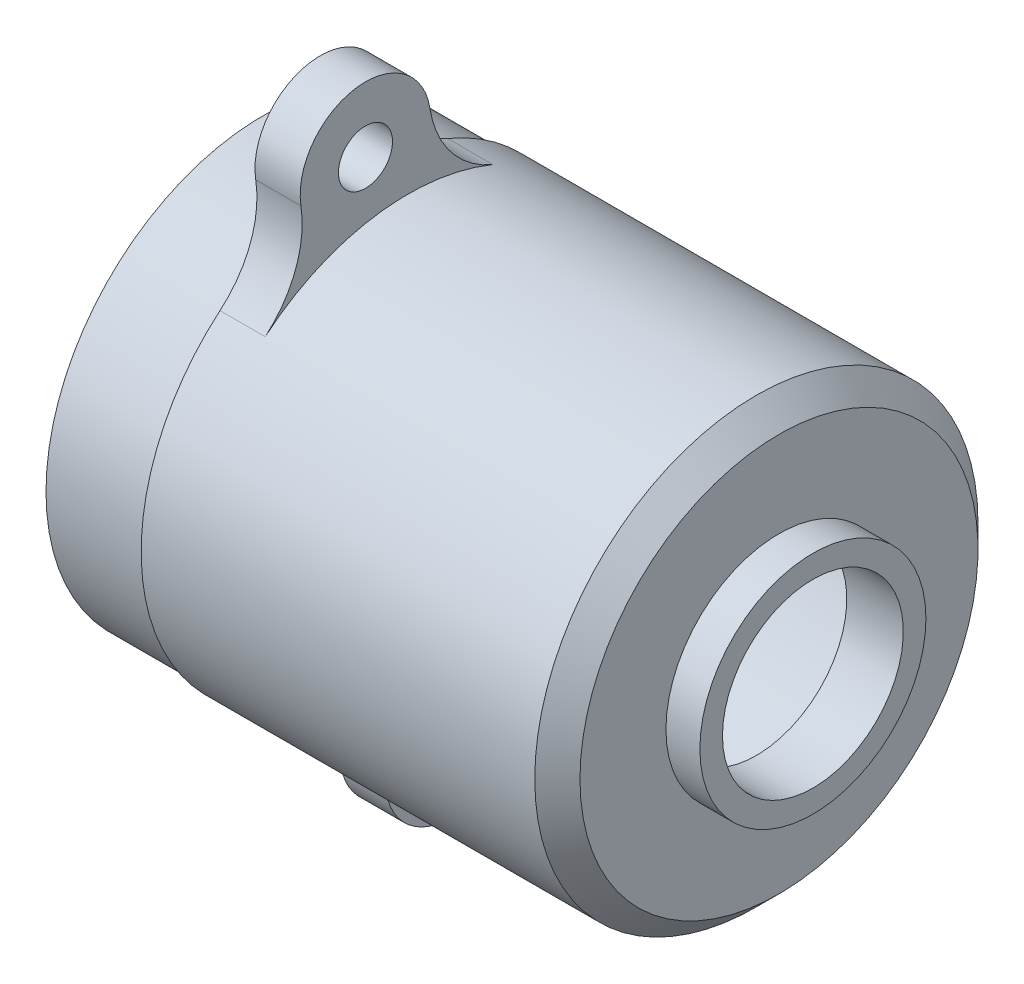
SolidWorks part; units mm, degrees
material "6061-T6 (SS)"
ref_plane "Front Plane" through (0, 0, 0) normal (0, 0, 1) x (1, 0, 0)
ref_plane "Top Plane" through (0, 0, 0) normal (0, 1, 0) x (1, 0, 0)
ref_plane "Right Plane" through (0, 0, 0) normal (1, 0, 0) x (0, 0, -1)
other "Center of Mass"
sketch "Sketch1" plane through (-31.75, 0, 0) normal (1, 0, 0) x (0, 0, -1)
  line L0 (0, 0) -> (-2.9885, 19.3009) construction
  line L1 (-0.1168, 15.7295) -> (1.5403, 20.0021) construction
  line L2 (1.5403, 20.0021) -> (-1.3314, 23.5735) construction
  line L3 (-1.3314, 23.5735) -> (-5.8601, 22.8723) construction
  line L4 (-5.8601, 22.8723) -> (-7.5172, 18.5996) construction
  line L5 (-7.5172, 18.5996) -> (-4.6456, 15.0282) construction
  line L6 (-4.6456, 15.0282) -> (-0.1168, 15.7295) construction
  line L7 (4.6456, -15.0282) -> (0.1168, -15.7295) construction
  line L8 (0.1168, -15.7295) -> (-1.5403, -20.0021) construction
  line L9 (-1.5403, -20.0021) -> (1.3314, -23.5735) construction
  line L10 (1.3314, -23.5735) -> (5.8601, -22.8723) construction
  line L11 (5.8601, -22.8723) -> (7.5172, -18.5996) construction
  line L12 (7.5172, -18.5996) -> (4.6456, -15.0282) construction
  line L13 (-7.5172, 18.5996) -> (1.5403, 20.0021) construction
  line L15 (0, 0) -> (12.0771, 1.87) construction
  circle A0 centre (0, 0) radius 13.9746
  circle A1 centre (0, 0) radius 15.5621 construction
  circle A3 centre (2.9885, -19.3009) radius 3.9688 construction
  circle A4 centre (-2.9885, 19.3009) radius 8.7404 construction
  arc A8 (-10.0273, 11.901) -> (-5.9586, -14.3762) centre (0, 0) ccw
  arc A9 (5.9586, 14.3762) -> (10.0273, -11.901) centre (0, 0) cw
  circle A16 centre (-2.9885, 19.3009) radius 2.667 construction
  circle A17 centre (2.9885, -19.3009) radius 2.667 construction
  arc A18 (-9.6776, 36.4316) -> (-11.5083, 22.6659) centre (127.0686, 11.2409) ccw construction
  arc A19 (4.4842, 36.4316) -> (4.6143, 28.807) centre (76.9988, 33.8561) ccw construction
  arc A20 (-10.0273, 11.901) -> (-7.5172, 18.5996) centre (-14.7303, 17.4828) ccw
  arc A21 (-7.5172, 18.5996) -> (1.5403, 20.0021) centre (-2.9885, 19.3009) cw
  arc A22 (1.5403, 20.0021) -> (5.9586, 14.3762) centre (8.7533, 21.1189) ccw
  arc A23 (7.5172, -18.5996) -> (10.0273, -11.901) centre (14.7303, -17.4828) cw
  arc A24 (-1.5403, -20.0021) -> (7.5172, -18.5996) centre (2.9885, -19.3009) ccw
  arc A25 (-5.9586, -14.3762) -> (-1.5403, -20.0021) centre (-8.7533, -21.1189) cw
  point P4 (-2.3812, 15.3788)
  dimension "D1" = 27.9492
  dimension "D4" = 5.334
  dimension "D2" = 1.5875
  dimension "D3" = 7.9375
extrude "Boss-Extrude1" add sketch "Sketch1" along normal blind 3.175
sketch "Sketch2" plane through (-28.575, 0, 0) normal (1, 0, 0) x (0, 0, -1)
  circle A0 centre (0, 0) radius 13.9746
  circle A1 centre (0, 0) radius 15.5621
  arc A2 (-10.0273, 11.901) -> (-5.9586, -14.3762) centre (0, 0) ccw construction
  circle A3 centre (0, 0) radius 13.9746 construction
extrude "Boss-Extrude2" add sketch "Sketch2" along normal up to surface (24.4625 mm away)
sketch "Sketch5" plane through (0, 0, 0) normal (0, 0, 1) x (1, 0, 0)
  line L1 (-0.1437, 7.9375) -> (-0.1437, 6.35)
  line L3 (-4.1125, -15.5621) -> (-4.1125, 15.5621) construction
  line L4 (-4.1125, 6.35) -> (-4.1125, 15.5621)
  line L5 (0, 0) -> (45.5597, 0) construction
  line L6 (-4.1125, 6.35) -> (-0.1437, 6.35)
  line L9 (-0.1437, 7.9375) -> (-2.525, 7.9375)
  line L10 (-2.525, 7.9375) -> (-2.525, 13.9746)
  line L11 (-2.525, 13.9746) -> (-4.1125, 15.5621)
  dimension "D2" = 3.9688
  dimension "D1" = 12.7
  dimension "D3" = 1.5875
  dimension "D4" = 1.5875
  dimension "D5" = 45
revolve "Revolve1" add sketch "Sketch5" angle 360 about L5
sketch "Sketch3" plane through (-31.75, 0, 0) normal (-1, 0, 0) x (0, 0, 1)
  circle A0 centre (0, 0) radius 13.9746
  circle A1 centre (0, 0) radius 15.2446
  circle A2 centre (0, 0) radius 13.9746 construction
  dimension "D1" = 1.27
extrude "Boss-Extrude3" add sketch "Sketch3" along normal blind 7
sketch "Sketch6" plane through (0, 0, 0) normal (0, 0, 1) x (1, 0, 0)
  line L0 (-31.75, -23.8836) -> (-31.5663, -23.8836)
  line L1 (-31.75, -23.8836) -> (-28.575, -23.8836) construction
  line L2 (-31.75, -23.8836) -> (-31.75, -25.4)
  line L3 (-31.75, -18.5996) -> (-31.75, -23.8836) construction
  arc A0 (-31.75, -25.4) -> (-31.3998, -27.4796) centre (-25.4, -25.4) ccw construction
  arc A1 (-31.5663, -23.8836) -> (-31.75, -25.4) centre (-25.4, -25.4) cw
extrude "Cut-Extrude1" [suppressed] cut sketch "Sketch6" against normal through all both and the other way through all
hole_wizard "#6 Clearance Hole1" positions "Sketch7" profile "Sketch8" hole size "#6" standard "ANSI Inch" end condition up to next
sketch "Sketch7" plane through (-28.575, 0, 0) normal (1, 0, 0) x (0, 0, -1)
  point P0 (-2.9885, 19.3009)
  point P3 (2.9885, -19.3009)
sketch "Sketch8" plane through (-28.575, 19.3009, 2.9885) normal (0, 1, 0) x (0, 0, -1)
  line L0 (0, 0) -> (0, 3.175)
  line L1 (0, 3.175) -> (1.8986, 3.175)
  line L2 (1.8986, 3.175) -> (1.8986, 0)
  line L5 (1.8986, 0) -> (0, 0)
  line L11 (0, -6.35) -> (0, 107.95) construction
  dimension "Thru Hole Dia." = 3.7973
  dimension "Thru Hole Depth" = 3.175
equation "\"motor diameter\"= 28mm"
equation "\"D1@Sketch1\"=\"motor diameter\"-0.002in"
equation "\"D1@Boss-Extrude3\"=7mm"
equation "\"D2@Sketch5\"=5/32"
